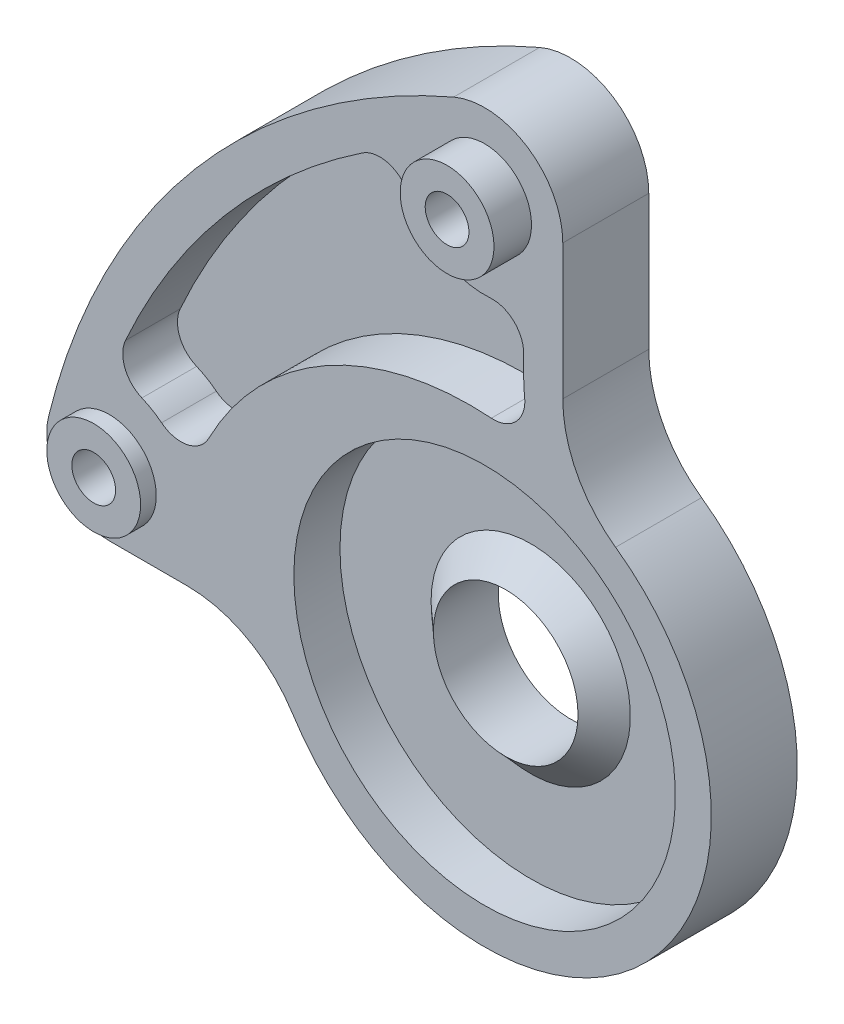
SolidWorks part; units mm, degrees
material "PLA_Shoulder"
ref_plane "Front Plane" through (0, 0, 0) normal (0, 0, 1) x (1, 0, 0)
ref_plane "Top Plane" through (0, 0, 0) normal (0, 1, 0) x (1, 0, 0)
ref_plane "Right Plane" through (0, 0, 0) normal (1, 0, 0) x (0, 0, -1)
ref_plane "Plane1" through (0, 0, 5.5) normal (0, 0, 1) x (1, 0, 0)
sketch "Sketch1" plane through (0, 0, 5.5) normal (0, 0, 1) x (1, 0, 0)
  line L0 (5, 18.3644) -> (5, 27)
  line L1 (-24, -4) -> (-19.0329, -4)
  arc A0 (8.3778, 11.8348) -> (5, 18.3644) centre (13, 18.3644) cw
  arc A1 (5, 27) -> (-1.9784, 31.5919) centre (0, 27) ccw
  arc A2 (-1.9784, 31.5919) -> (-27.8856, 0.9498) centre (15.8274, -9.7355) ccw
  arc A3 (-27.8856, 0.9498) -> (-24, -4) centre (-24, 0) ccw
  arc A4 (-19.0329, -4) -> (-12.2656, -7.7333) centre (-19.0329, -12) cw
  arc A5 (-12.2656, -7.7333) -> (8.3778, 11.8348) centre (0, 0) ccw
extrude "Boss-Extrude1" add sketch "Sketch1" against normal blind 5.5
sketch "Sketch2" plane through (0, 0, 5.5) normal (0, 0, 1) x (1, 0, 0)
  circle A0 centre (0, 27) radius 3
  dimension "D1" = 6
extrude "Boss-Extrude2" add sketch "Sketch2" along normal blind 2.4
sketch "Sketch3" plane through (0, 0, 5.5) normal (0, 0, 1) x (1, 0, 0)
  circle A0 centre (-24, 0) radius 3
  dimension "D1" = 6
extrude "Boss-Extrude3" add sketch "Sketch3" along normal blind 1
sketch "Sketch4" plane through (0, 0, 0) normal (0, 0, -1) x (-1, 0, 0)
  circle A0 centre (0, 0) radius 4.625
  dimension "D1" = 9.25
extrude "Cut-Extrude1" cut sketch "Sketch4" against normal through all
sketch "Sketch5" plane through (0, 0, 7.9) normal (0, 0, 1) x (1, 0, 0)
  circle A0 centre (0, 27) radius 1.4
  circle A1 centre (-24, 0) radius 1.4
  dimension "D1" = 2.8
extrude "Cut-Extrude2" cut sketch "Sketch5" against normal through all
sketch "Sketch7" plane through (0, 0, 5.5) normal (0, 0, 1) x (1, 0, 0)
  circle A0 centre (0, 0) radius 12.2
  circle A1 centre (0, 0) radius 12.1 construction
  dimension "D1" = 0.1
  dimension "D2" = 24.2
extrude "Cut-Extrude4" cut sketch "Sketch7" against normal blind 2.95
sketch "Sketch8" plane through (0, 0, 5.5) normal (0, 0, 1) x (1, 0, 0)
  line L0 (2.5, 18.3644) -> (2.5, 19.6403)
  arc A0 (0.3644, 21.6357) -> (-4.8853, 24.7546) centre (0, 27) cw
  arc A1 (-4.8853, 24.7546) -> (-7.8152, 25.5814) centre (-6.7026, 23.9194) ccw
  arc A2 (-7.8152, 25.5814) -> (-22.9686, 7.6175) centre (15.8274, -9.7355) ccw
  arc A3 (-22.9686, 7.6175) -> (-21.9175, 4.957) centre (-21.1429, 6.8009) ccw
  arc A4 (-21.9175, 4.957) -> (-20.6588, 4.2124) centre (-24, 0) cw
  arc A5 (-20.6588, 4.2124) -> (-17.6384, 4.8627) centre (-19.4159, 5.7794) ccw
  arc A6 (-17.6384, 4.8627) -> (0.4318, 15.0138) centre (-0.9047, -3.7663) cw
  arc A7 (0.4318, 15.0138) -> (2.5619, 17.2256) centre (0.5737, 17.0087) ccw
  arc A8 (2.5619, 17.2256) -> (2.5, 18.3644) centre (13, 18.3644) cw
  arc A9 (2.5, 19.6403) -> (0.3644, 21.6357) centre (0.5, 19.6403) ccw
extrude "Cut-Extrude5" cut sketch "Sketch8" against normal blind 3.5
sketch "Sketch9" plane through (0, 0, 2.55) normal (0, 0, 1) x (1, 0, 0)
  circle A0 centre (0, 0) radius 4.625 construction
  circle A1 centre (0, 0) radius 4.625
  circle A3 centre (0, 0) radius 6.375
  dimension "D2" = 1.75
extrude "Boss-Extrude4" add sketch "Sketch9" along normal blind 1.6
chamfer "Chamfer1" distance 1.6 distance2 1.75 1 edges at (6.375, 0, 4.15) first distance on face at (6.375, 0, 4.15)
